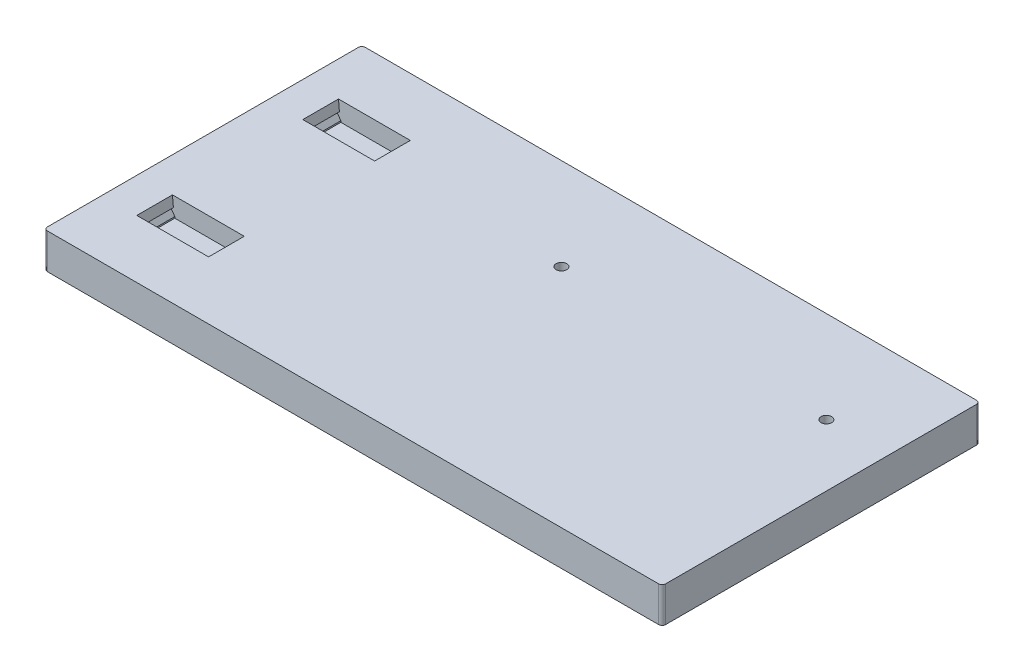
SolidWorks part; units mm, degrees
ref_plane "Front Plane" through (0, 0, 0) normal (0, 0, 1) x (1, 0, 0)
ref_plane "Top Plane" through (0, 0, 0) normal (0, 1, 0) x (1, 0, 0)
ref_plane "Right Plane" through (0, 0, 0) normal (1, 0, 0) x (0, 0, -1)
sketch "Sketch1" plane through (0, 0, 0) normal (0, 1, 0) x (1, 0, 0)
  line L1 (87.5, -45) -> (-87.5, -45)
  line L2 (87.5, -45) -> (87.5, 45)
  line L3 (87.5, 45) -> (-87.5, 45)
  line L4 (-87.5, -45) -> (-87.5, 45)
  line L5 (87.5, -45) -> (-87.5, 45) construction
  line L6 (87.5, 45) -> (-87.5, -45) construction
  point P0 (0, 0)
  dimension "D1" = 175
  dimension "D2" = 90
extrude "Boss-Extrude1" add sketch "Sketch1" along normal blind 10
sketch "Sketch2" plane through (0, 10, 0) normal (0, 1, 0) x (1, 0, 0)
  line L0 (-87.5, 45) -> (-87.5, -45) construction
  line L5 (-67.5, -23.5) -> (-67.5, 0) construction
  line L6 (-77, -28.55) -> (-58, -28.55)
  line L7 (0, 0) -> (-87.5, 0) construction
  line L8 (-77, -28.55) -> (-77, -18.45)
  line L9 (-77, -18.45) -> (-58, -18.45)
  line L10 (-58, -28.55) -> (-58, -18.45)
  line L11 (-77, -28.55) -> (-58, -18.45) construction
  line L12 (-77, -18.45) -> (-58, -28.55) construction
  circle A0 centre (-5, 19) radius 1.5
  circle A1 centre (70, 19) radius 1.5
  point P0 (-67.5, -23.5)
  dimension "D6" = 19
  dimension "D8" = 3
  dimension "D1" = 19
  dimension "D2" = 10.1
  dimension "D3" = 23.5
  dimension "D4" = 20
  dimension "D5" = 62.5
  dimension "D7" = 75
extrude "Cut-Extrude1" cut sketch "Sketch2" against normal blind 5.4 contours L6 L10 L9 L8 region at (-67.5, 10, 23.5)
ref_plane "Plane1" through (0, 0, 18.45) normal (0, 0, 1) x (1, 0, 0)
sketch "Sketch7" plane through (0, 0, 18.45) normal (0, 0, 1) x (1, 0, 0)
  line L0 (-77, 5) -> (-77, 10)
  line L12 (-77, 4.6) -> (-58, 4.6) construction
  line L14 (-67.5, 10) -> (-67.5, 4.6) construction
  line L15 (-77, 10) -> (-58, 10) construction
  line L27 (-77, 5) -> (-78.4004, 7)
  line L28 (-78.4004, 7) -> (-77.4004, 7)
  line L29 (-77.4004, 7) -> (-77.6629, 10)
  line L30 (-77.6629, 10) -> (-77, 10)
  line L38 (-77, 5) -> (-75.9078, 5) construction
  line L40 (-87.5, 10) -> (87.5, 10) construction
  line L41 (-58, 5) -> (-59.0922, 5) construction
  line L42 (-58, 5) -> (-58, 10) construction
  line L43 (-58, 5) -> (-58, 10)
  line L44 (-57.3371, 10) -> (-58, 10)
  line L45 (-57.5996, 7) -> (-57.3371, 10)
  line L46 (-56.5996, 7) -> (-57.5996, 7)
  line L47 (-58, 5) -> (-56.5996, 7)
  dimension "D1" = 125
  dimension "D2" = 95
  dimension "D3" = 1
  dimension "D4" = 2
  dimension "D5" = 5
extrude "Cut-Extrude2" cut sketch "Sketch7" along normal up to surface (10.1 mm away) up to face at (-67.5, 7.3, 28.55)
mirror "Mirror1" about plane through (0, 0, 0) normal (0, 0, 1) of "Cut-Extrude2", "Cut-Extrude1"
fillet "Fillet1" radius 1 4 edges at (-87.5, 5, -45) (87.5, 5, -45) (87.5, 5, 45) (-87.5, 5, 45)
extrude "Cut-Extrude3" cut sketch "Sketch2<8>" against normal through all contours A0 | A1
sketch "Sketch2<8>" plane through (0, 10, 0) normal (0, 1, 0) x (1, 0, 0) same geometry as "Sketch2"
